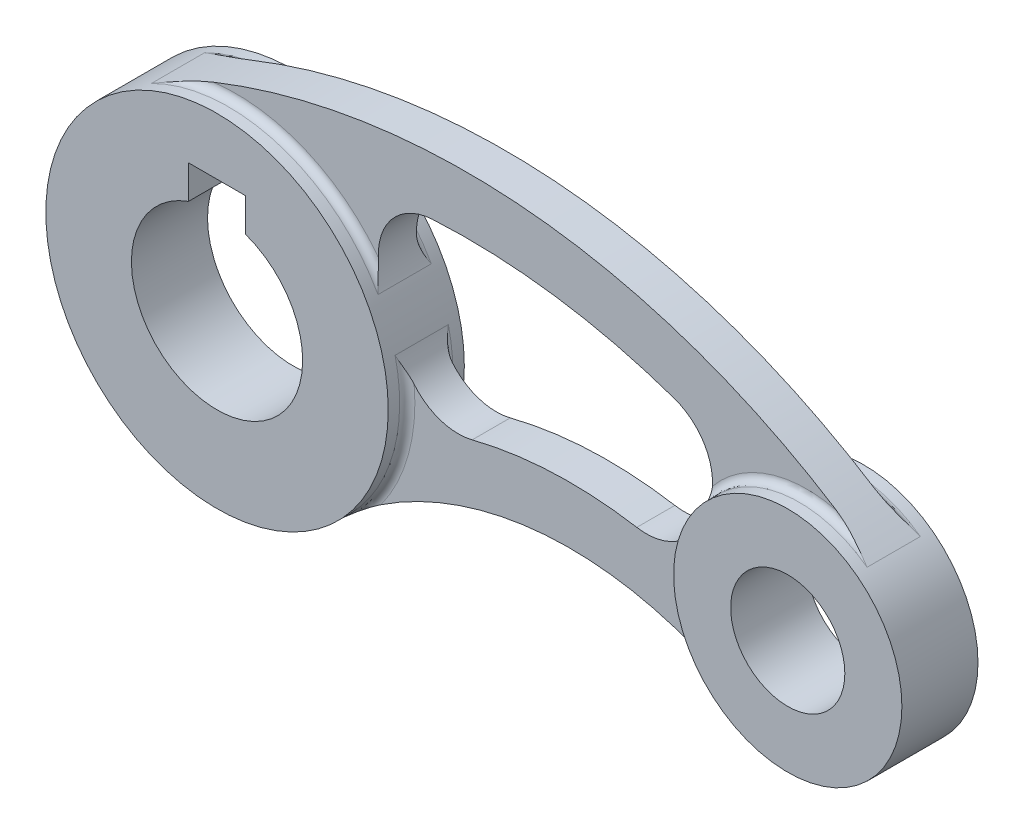
SolidWorks part; units mm, degrees
material "Plain Carbon Steel"
ref_plane "Front Plane" through (0, 0, 0) normal (0, 0, 1) x (1, 0, 0)
ref_plane "Top Plane" through (0, 0, 0) normal (0, 1, 0) x (1, 0, 0)
ref_plane "Right Plane" through (0, 0, 0) normal (1, 0, 0) x (0, 0, -1)
sketch "Sketch1" plane through (0, 0, 0) normal (0, 0, 1) x (1, 0, 0)
  line L0 (0, 0) -> (150, 0) construction
  line L1 (0, 30) -> (0, 0) construction
  line L2 (-7.5, 30) -> (7.5, 30)
  line L3 (-7.5, 30) -> (-7.5, 21.2132)
  line L5 (7.5, 30) -> (7.5, 21.2132)
  arc A0 (-7.5, 21.2132) -> (7.5, 21.2132) centre (0, 0) ccw
  circle A1 centre (150, 0) radius 15
  circle A2 centre (0, 0) radius 45
  circle A3 centre (150, 0) radius 30
  arc A4 (-20.25, 40.1863) -> (167.85, 24.1118) centre (60.75, -120.5589) cw
  arc A5 (29.25, -34.197) -> (134.4375, -25.6478) centre (87.75, -102.5911) cw
  arc A6 (51.5762, 44.1859) -> (115.1728, 35.2075) centre (60.75, -120.5589) cw
  arc A7 (62.0686, -0.7802) -> (105.3232, 0.9279) centre (87.75, -102.5911) cw
  arc A8 (51.5762, 44.1859) -> (39.3076, 21.9068) centre (52.4102, 29.2091) ccw
  arc A9 (19.5, -22.798) -> (142.2187, -12.8239) centre (87.75, -102.5911) cw construction
  arc A10 (-13.5, 26.7909) -> (158.925, 12.0559) centre (60.75, -120.5589) cw construction
  arc A11 (115.1728, 35.2075) -> (123.4835, 14.0313) centre (110.2253, 21.0469) cw
  arc A12 (62.0686, -0.7802) -> (43.7999, 10.3232) centre (58.3999, 13.7642) cw
  arc A13 (105.3232, 0.9279) -> (121.8891, 10.4775) centre (107.8337, 15.7163) ccw
  arc A14 (-7.5, 21.2132) -> (7.5, 21.2132) centre (0, 0) cw
  dimension "A" = 30
  dimension "D1" = 90
  dimension "D2" = 60
  dimension "D3" = 45
  dimension "D4" = 180
  dimension "D5" = 90
  dimension "D8" = 15
  dimension "D9" = 15
  dimension "D10" = 15
  dimension "D11" = 15
  dimension "B" = 150
  dimension "D13" = 15
  dimension "D12" = 30
  dimension "D6" = 15
  dimension "D7" = 15
extrude "Boss-Extrude1" add sketch "Sketch1" along normal mid plane 20 contours A2 A0 | A3 A1 region at (39.7172, -18.2924, 0) region at (122.4625, -9.5653, 0)
extrude "Boss-Extrude3" add sketch "Sketch1<5>" along normal mid plane 10 contours A6 A11 A3 A4 A2 A8 | A13 A7 A12 A2 A5 A3 region at (81.0787, -8.104, 0) region at (76.8412, 45.0062, 0)
sketch "Sketch1<5>" plane through (0, 0, 0) normal (0, 0, 1) x (1, 0, 0) same geometry as "Sketch1"
fillet "Fillet2" radius 2 8 edges at (42.7736, -13.9791, -5) (13.2035, 43.0194, -5) (121.661, -9.8438, -5) (143.3531, 29.2544, -5) (121.661, -9.8438, 5) (42.7736, -13.9791, 5) (143.3531, 29.2544, 5) (13.2035, 43.0194, 5)
equation "\"gl\"= 30"
equation "\"A@Sketch1\" = \"gl\""
equation "\"glo\"= 150"
equation "\"B@Sketch1\" = \"glo\""
equation "\"C\"= 15"
equation "\"D6@Sketch1\"=\"C\""
equation "\"D7@Sketch1\"= \"C\""
equation "\"D2@Sketch1\"= \"gl\" * 2"
equation "\"D10@Sketch1\"= \"C\""
equation "\"D5@Sketch1\"= \"gl\" * 3"
equation "\"D9@Sketch1\"= \"C\""
equation "\"D8@Sketch1\"= \"C\""
equation "\"D11@Sketch1\"= \"C\""
equation "\"D3@Sketch1\"= \"gl\" * 1.5"
equation "\"D1@Sketch1\"= \"gl\" * 3"
equation "\"D13@Sketch1\"= \"C\"' "
equation "\"D4@Sketch1\"= \"gl\" * 6"
equation "\"D12@Sketch1\"=\"C\"/2 + \"gl\"*1.5/2"
